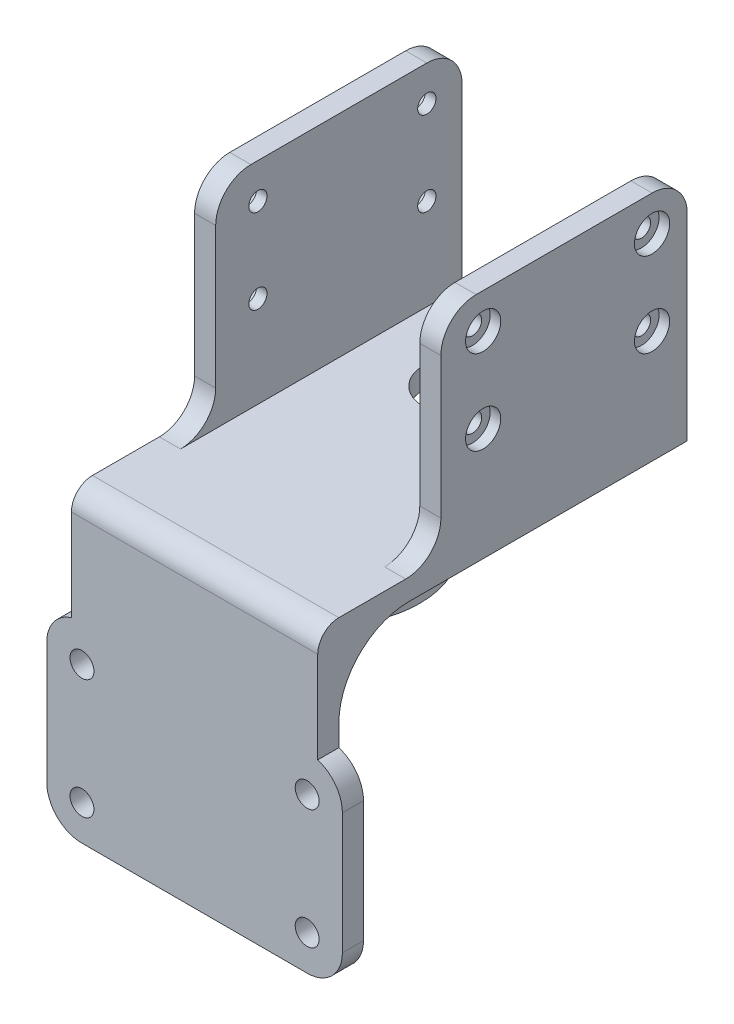
SolidWorks part; units mm, degrees
ref_plane "Front Plane" through (0, 0, 0) normal (0, 0, 1) x (1, 0, 0)
ref_plane "Top Plane" through (0, 0, 0) normal (0, 1, 0) x (1, 0, 0)
ref_plane "Right Plane" through (0, 0, 0) normal (1, 0, 0) x (0, 0, -1)
sketch "Sketch1" plane through (0, 0, 0) normal (0, 1, 0) x (1, 0, 0)
  line L0 (-14.5, 17.5) -> (-17.5, 17.5)
  line L1 (-17.5, 17.5) -> (-17.5, -17.5)
  line L2 (-17.5, -17.5) -> (-14.5, -17.5)
  line L3 (-14.5, -17.5) -> (-14.5, 17.5)
  line L4 (0, 0) -> (0, 50) construction
  line L5 (14.5, -17.5) -> (14.5, 17.5)
  line L6 (17.5, -17.5) -> (14.5, -17.5)
  line L7 (17.5, 17.5) -> (17.5, -17.5)
  line L8 (14.5, 17.5) -> (17.5, 17.5)
  point P7 (-14.5, 0)
  dimension "D1" = 50
  dimension "D2" = 35
  dimension "D3" = 3
  dimension "D4" = 29
extrude "Boss-Extrude1" add sketch "Sketch1" along normal blind 22
sketch "Sketch2" plane through (-17.5, 0, 0) normal (-1, 0, 0) x (0, 0, 1)
  line L0 (-17.5, 22) -> (17.5, 22) construction
  line L1 (-17.5, 22) -> (-17.5, 0) construction
  circle A0 centre (-12.5, 17) radius 1.3
  circle A1 centre (11.5, 17) radius 1.3
  circle A2 centre (11.5, 5) radius 1.3
  circle A3 centre (-12.5, 5) radius 1.3
  dimension "D1" = 2.6
  dimension "D4" = 5
  dimension "D5" = 5
  dimension "D2" = 2
  dimension "D3" = 2
extrude "Cut-Extrude1" cut sketch "Sketch2" against normal through all
sketch "Sketch3" plane through (-17.5, 0, 0) normal (-1, 0, 0) x (0, 0, 1)
  line L0 (-17.5, 11) -> (17.5, 11) construction
  line L1 (-17.5, 22) -> (-17.5, 0) construction
  line L2 (17.5, 22) -> (17.5, 0) construction
sketch "Sketch4" plane through (0, 0, 0) normal (0, -1, 0) x (1, 0, 0)
  line L0 (17.5, -17.5) -> (14.5, -17.5) construction
  line L1 (-17.5, 17.5) -> (-14.5, 17.5)
  line L2 (-17.5, 17.5) -> (-17.5, -17.5)
  line L3 (-17.5, -17.5) -> (-14.5, -17.5)
  line L4 (-14.5, 17.5) -> (-14.5, -17.5)
  line L5 (14.5, 17.5) -> (17.5, 17.5)
  line L6 (14.5, 17.5) -> (14.5, -17.5)
  line L7 (14.5, -17.5) -> (17.5, -17.5)
  line L8 (17.5, 17.5) -> (17.5, -17.5)
  line L9 (17.5, 17.5) -> (17.5, -17.5) construction
extrude "Boss-Extrude3" add sketch "Sketch4" along normal blind 8
sketch "Sketch5" plane through (0, -8, 0) normal (0, -1, 0) x (1, 0, 0)
  line L0 (17.5, -17.5) -> (17.5, 17.5) construction
  line L1 (-17.5, 17.5) -> (17.5, 17.5)
  line L2 (-17.5, 17.5) -> (-17.5, -17.5)
  line L3 (-17.5, -17.5) -> (-7.5, -17.5)
  line L4 (17.5, 17.5) -> (17.5, -17.5)
  line L5 (7.5, -17.5) -> (17.5, -17.5)
  line L7 (7.5, -17.5) -> (7.5, 0)
  line L8 (7.5, 0) -> (-7.5, 0)
  line L9 (-7.5, -17.5) -> (-7.5, 0)
  point P12 (0, 0)
  dimension "D1" = 15
extrude "Boss-Extrude4" add sketch "Sketch5" along normal blind 3
sketch "Sketch7" plane through (0, -11, 0) normal (0, -1, 0) x (1, 0, 0)
  line L0 (17.5, 17.5) -> (-17.5, 17.5) construction
  circle A0 centre (0, 16.5) radius 13.5
  dimension "D1" = 1
  dimension "D2" = 27
extrude "Boss-Extrude5" add sketch "Sketch7" along normal blind 5
sketch "Sketch8" plane through (0, -16, 0) normal (0, -1, 0) x (-1, 0, 0)
  circle A0 centre (0, -16.5) radius 11.75
  dimension "D1" = 23.5
extrude "Cut-Extrude2" cut sketch "Sketch8" against normal blind 3
sketch "Sketch9" plane through (-17.5, 0, 0) normal (-1, 0, 0) x (0, 0, 1)
  circle A0 centre (-12.5, 17) radius 2.5
  circle A1 centre (11.5, 17) radius 2.5
  circle A2 centre (11.5, 5) radius 2.5
  circle A3 centre (-12.5, 5) radius 2.5
  dimension "D1" = 5
  dimension "D2" = 2
  dimension "D3" = 2
extrude "Cut-Extrude3" cut sketch "Sketch9" against normal blind 1.5
sketch "Sketch10" plane through (17.5, 0, 0) normal (1, 0, 0) x (0, 0, -1)
  circle A0 centre (-11.5, 17) radius 2.5
  circle A1 centre (12.5, 17) radius 2.5
  circle A2 centre (12.5, 5) radius 2.5
  circle A3 centre (-11.5, 5) radius 2.5
  dimension "D1" = 5
  dimension "D2" = 2
  dimension "D3" = 2
extrude "Cut-Extrude4" cut sketch "Sketch10" against normal blind 1.5
sketch "Sketch11" plane through (0, 0, 17.5) normal (0, 0, 1) x (1, 0, 0)
  line L0 (-17.5, 22) -> (-17.5, -11) construction
  line L1 (17.5, -11) -> (-17.5, -11)
  line L2 (17.5, -11) -> (17.5, -8)
  line L3 (17.5, -8) -> (-17.5, -8)
  line L4 (-17.5, -11) -> (-17.5, -8)
  dimension "D1" = 3
extrude "Boss-Extrude6" add sketch "Sketch11" along normal blind 17.5
sketch "Sketch13" plane through (0, -11, 0) normal (0, -1, 0) x (1, 0, 0)
  line L0 (17.5, -17.5) -> (17.5, 35) construction
  line L1 (-17.5, 35) -> (17.5, 35)
  line L2 (-17.5, 35) -> (-17.5, 32)
  line L3 (-17.5, 32) -> (17.5, 32)
  line L4 (17.5, 35) -> (17.5, 32)
  dimension "D1" = 3
extrude "Boss-Extrude7" add sketch "Sketch13" along normal blind 40
sketch "Sketch14" plane through (0, 0, 35) normal (0, 0, 1) x (1, 0, 0)
  line L1 (-21, -24) -> (21, -24)
  line L2 (-21, -24) -> (-21, -51)
  line L3 (-21, -51) -> (21, -51)
  line L4 (21, -24) -> (21, -51)
  line L5 (17.5, -51) -> (-17.5, -51) construction
  point P4 (0, 0)
  point P5 (0, 0)
  point P7 (0, -51)
  point P9 (-23.373, -48.8862)
  point P11 (0, -51)
  dimension "D1" = 42
  dimension "D2" = 27
extrude "Boss-Extrude8" add sketch "Sketch14" against normal up to surface (3 mm away) up to face at (0, -31, 32)
sketch "Sketch15" plane through (0, 0, 35) normal (0, 0, 1) x (1, 0, 0)
  line L0 (-21, -24) -> (-21, -51) construction
  line L1 (-17.5, -24) -> (-21, -24) construction
  circle A0 centre (-16, -29) radius 1.7
  circle A1 centre (16, -29) radius 1.7
  circle A2 centre (16, -46) radius 1.7
  circle A3 centre (-16, -46) radius 1.7
  dimension "D1" = 3.4
  dimension "D2" = 5
  dimension "D3" = 5
  dimension "D4" = 2
  dimension "D5" = 2
extrude "Cut-Extrude5" cut sketch "Sketch15" against normal blind 40
fillet "Fillet1" radius 10 1 edges at (0, -11, 32)
fillet "Fillet2" radius 5 14 edges at (16, -8, 17.5) (-16, -8, 17.5) (21, -24, 33.5) (-21, -24, 33.5) (21, -51, 33.5) (-21, -51, 33.5) (16, 22, 17.5) (-16, 22, 17.5) (-16, 22, -17.5) (-7.5, -9.5, -17.5) (-7.5, -9.5, 0) (7.5, -9.5, 0) (7.5, -9.5, -17.5) (16, 22, -17.5)
fillet "Fillet3" radius 3 1 edges at (0, -8, 35)
